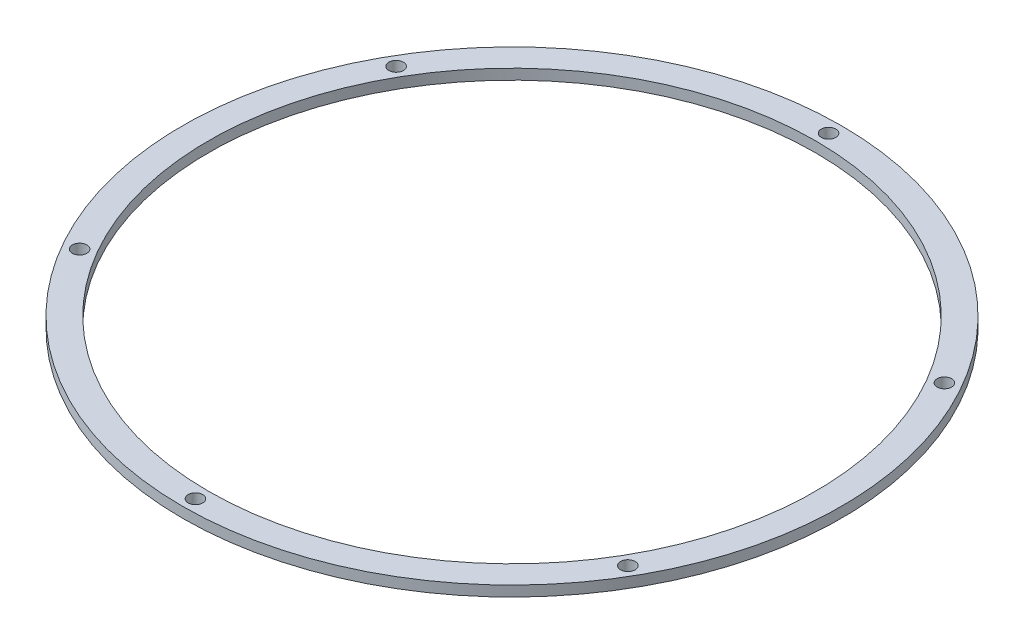
SolidWorks part; units mm, degrees
ref_plane "Front Plane" through (0, 0, 0) normal (0, 0, 1) x (1, 0, 0)
ref_plane "Top Plane" through (0, 0, 0) normal (0, 1, 0) x (1, 0, 0)
ref_plane "Right Plane" through (0, 0, 0) normal (1, 0, 0) x (0, 0, -1)
sketch "Sketch1" plane through (0, 0, 0) normal (0, 1, 0) x (1, 0, 0)
  line L0 (0, 154.5) -> (0, 0) construction
  line L1 (0, 160.85) -> (0, 148.15) construction
  line L2 (0, -184.4198) -> (0, 184.4198) construction
  circle A0 centre (0, 0) radius 154.5 construction
  circle A1 centre (0, 154.5) radius 3.556
  circle A2 centre (133.8009, 77.25) radius 3.556
  circle A3 centre (133.8009, -77.25) radius 3.556
  circle A4 centre (0, -154.5) radius 3.556
  circle A5 centre (-133.8009, -77.25) radius 3.556
  circle A6 centre (-133.8009, 77.25) radius 3.556
  circle A7 centre (0, 0) radius 160.85
  circle A8 centre (0, 0) radius 148.15
  point P17 (0, 0)
  point P20 (0, 154.5)
  dimension "D1" = 7.112
  dimension "D2" = 309
  dimension "D6" = 12.7
  dimension "D4" = 60
  dimension "D5" = 60
  dimension "D3" = 6
extrude "Boss-Extrude1" add sketch "Sketch1" along normal blind 5.08
